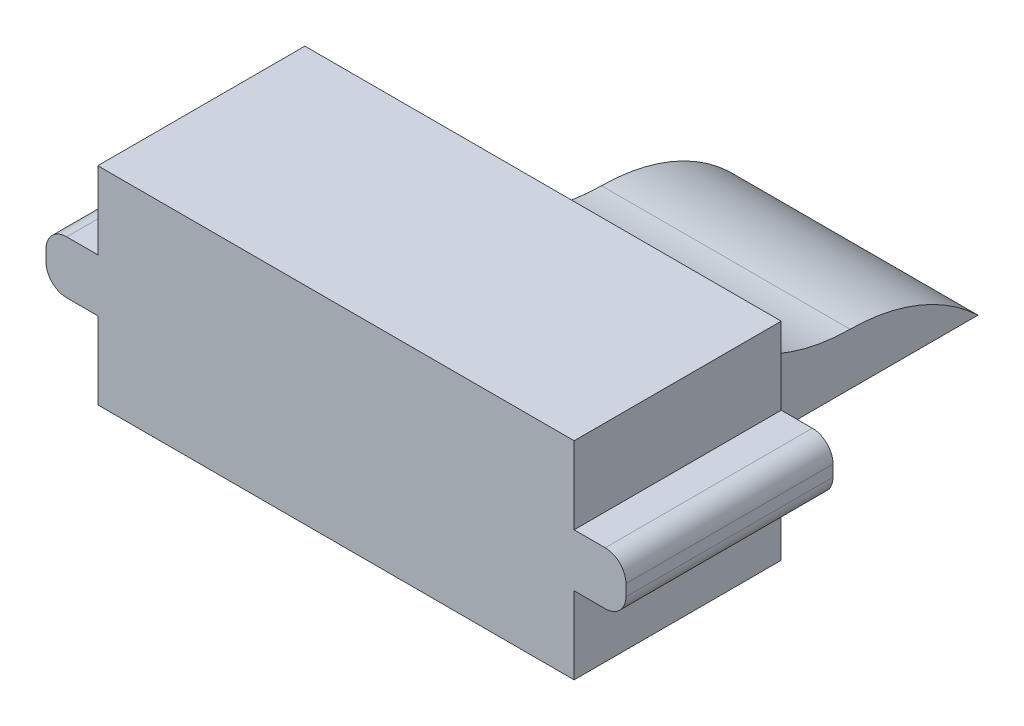
SolidWorks part; units mm, degrees
ref_plane "정면" through (0, 0, 0) normal (0, 0, 1) x (1, 0, 0)
ref_plane "윗면" through (0, 0, 0) normal (0, 1, 0) x (1, 0, 0)
ref_plane "우측면" through (0, 0, 0) normal (1, 0, 0) x (0, 0, -1)
sketch "스케치1" plane through (0, 0, 0) normal (0, 0, 1) x (1, 0, 0)
  line L1 (-23, 10) -> (23, 10)
  line L2 (-23, 10) -> (-23, -10)
  line L3 (-23, -10) -> (23, -10)
  line L4 (23, 10) -> (23, -10)
  line L5 (-23, 10) -> (23, -10) construction
  line L6 (-23, -10) -> (23, 10) construction
  point P0 (0, 0)
  dimension "D1" = 20
  dimension "D2" = 46
extrude "보스-돌출1" add sketch "스케치1" along normal blind 20
sketch "스케치2" plane through (-23, 0, 0) normal (-1, 0, 0) x (0, 0, 1)
  line L0 (20, 10) -> (20, -10) construction
  line L1 (0, 2.55) -> (20, 2.55)
  line L2 (0, 2.55) -> (0, -2.55)
  line L3 (0, -2.55) -> (20, -2.55)
  line L4 (20, 2.55) -> (20, -2.55)
  line L5 (0, 2.55) -> (20, -2.55) construction
  line L6 (0, -2.55) -> (20, 2.55) construction
  line L7 (0, 10) -> (0, -10) construction
  line L8 (20, -10) -> (0, -10) construction
  point P0 (10, 0)
  point P7 (0, 2.0346)
  point P10 (10, 0)
  dimension "D1" = 5.1
  dimension "D2" = 10
extrude "보스-돌출2" add sketch "스케치2" along normal blind 5
fillet "필렛1" radius 2 2 edges at (-28, 2.55, 10) (-28, -2.55, 10)
ref_plane "평면1" through (0, 0, 0) normal (1, 0, 0) x (0, 0, -1)
mirror "대칭 복사1" about plane through (0, 0, 0) normal (1, 0, 0) of "필렛1", "보스-돌출2"
sketch "스케치3" plane through (0, 0, 0) normal (0, 0, -1) x (-1, 0, 0)
  line L0 (23, -10) -> (-23, -10) construction
  line L1 (-12, -10) -> (12, -10)
  line L2 (-12, -10) -> (-12, -5)
  line L3 (-12, -5) -> (12, -5)
  line L4 (12, -10) -> (12, -5)
  line L5 (0, 11) -> (0, -11) construction
  dimension "D1" = 12
  dimension "D2" = 5
  dimension "D3" = 12
extrude "보스-돌출3" add sketch "스케치3" along normal blind 30
fillet "필렛2" radius 18 1 edges at (0, -5, 0)
fillet "필렛3" radius 18 1 edges at (0, -5, -30)
